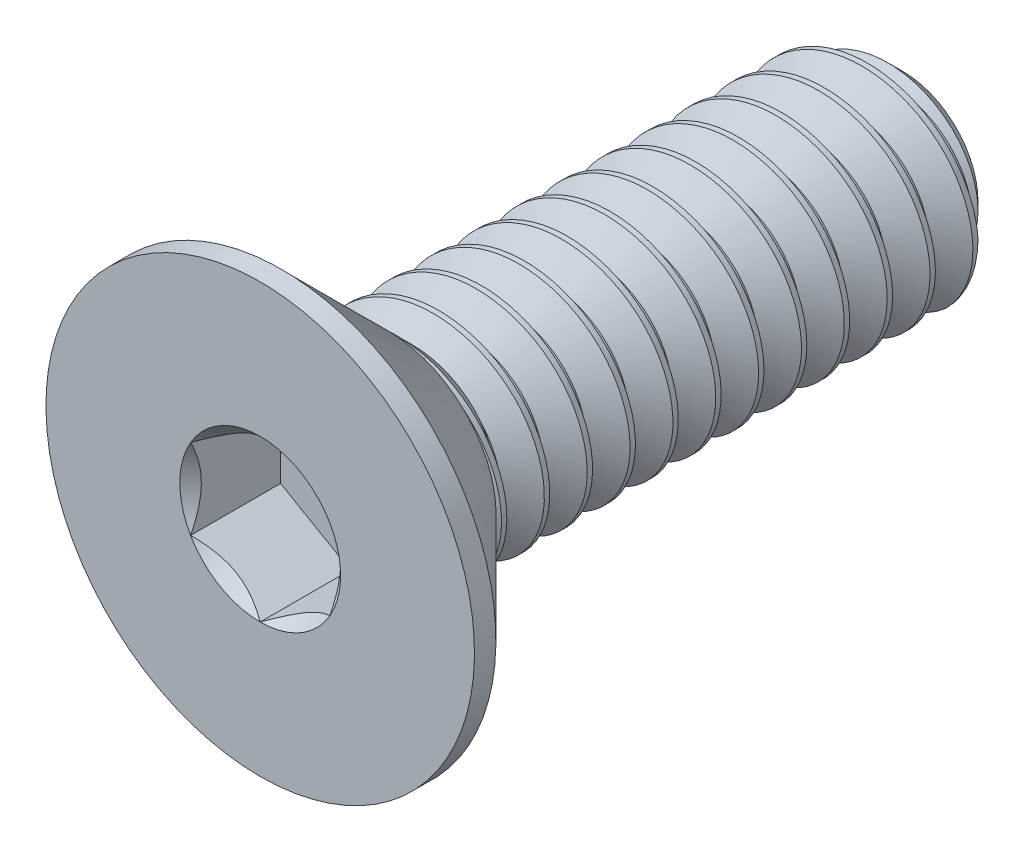
SolidWorks part; units mm, degrees
ref_plane "Front" through (0, 0, 0) normal (0, 0, 1) x (1, 0, 0)
ref_plane "Top" through (0, 0, 0) normal (0, 1, 0) x (1, 0, 0)
ref_plane "Right" through (0, 0, 0) normal (1, 0, 0) x (0, 0, -1)
sketch "Sketch1" plane through (0, 0, 0) normal (1, 0, 0) x (0, 0, -1)
  line L0 (0, 2) -> (0.2, 2) construction
  line L1 (0.2, 2) -> (1.2, 1) construction
  line L2 (0, 1) -> (6, 1)
  line L3 (6, 1) -> (6, 0)
  line L4 (6, 0) -> (0, 0)
  line L5 (0, 0) -> (0, 2) construction
  line L6 (0, 2) -> (0, -2) construction
  line L7 (6, 1) -> (6, -1) construction
  line L8 (0, -2) -> (0.2, -2) construction
  line L9 (0.2, -2) -> (1.2, -1) construction
  line L11 (0, 1) -> (0, 0)
  line L12 (1.2, 1) -> (1.2, 0) construction
  dimension "Head Ht" = 1.2
  dimension "Head Dia" = 4
  dimension "Dia" = 2
  dimension "Lg" = 6
  dimension "Head Angle" = 90
revolve "Revolve1" add sketch "Sketch1" angle 360 about L4
sketch "Sketch3" plane through (0, 0, -6) normal (0, 0, -1) x (-1, 0, 0)
  circle A0 centre (0, 0) radius 1
curve "Helix/Spiral1" pitch 0.4 height 6 radius 1 centre (0, 0, -6) axis (0, 0, 1) start towards (0, 1, 0)
sketch "Sketch2" plane through (0, 0, 0) normal (1, 0, 0) x (0, 0, -1)
  line L0 (6, 1) -> (6.35, 1)
  line L1 (6.35, 1) -> (6.2, 0.7402)
  line L2 (6.2, 0.7402) -> (6.15, 0.7402)
  line L3 (6.15, 0.7402) -> (6, 1)
  line L4 (6.075, 0.8701) -> (6.275, 0.8701) construction
  dimension "D1" = 60
  dimension "D2" = 0.05
  dimension "D3" = 0.2
chamfer "Chamfer1" distance 0.3 angle 45 1 edges at (0, 1, -6)
sweep "Cut-Sweep1" cut profiles "Sketch2" path "Helix/Spiral1"
sketch "Sketch7" plane through (0, 0, 0) normal (1, 0, 0) x (0, 0, -1)
  line L0 (0, 2) -> (0.2, 2) construction
  line L1 (0.2, 2) -> (1.2, 1) construction
  line L2 (0, 2) -> (0.2, 2)
  line L3 (0.2, 2) -> (1.2, 1)
  line L4 (1.2, 1) -> (1.2, 0) construction
  line L5 (1.2, 1) -> (1.2, 0)
  line L7 (0, 0) -> (0, 2) construction
  line L8 (0, 0) -> (0, 2)
  line L9 (0, 0) -> (1.2, 0)
  line L10 (2.2, 0) -> (-2.2, 0) construction
revolve "Revolve2" add sketch "Sketch7" angle 360 about L9
ref_plane "Plane1" through (0, 0, -1.2) normal (0, 0, 1) x (1, 0, 0)
sketch "Sketch8" plane through (0, 0, -1.2) normal (0, 0, 1) x (1, 0, 0)
  circle A0 centre (0, 0) radius 1
extrude "Boss-Extrude1" add sketch "Sketch8" against normal through all draft 45
sketch "Sketch5" plane through (0, 0, 0) normal (0, 0, 1) x (1, 0, 0)
  line L1 (0.65, -0.3753) -> (0.65, 0.3753)
  line L2 (0.65, 0.3753) -> (0, 0.7506)
  line L3 (0, 0.7506) -> (-0.65, 0.3753)
  line L4 (-0.65, 0.3753) -> (-0.65, -0.3753)
  line L5 (-0.65, -0.3753) -> (0, -0.7506)
  line L6 (0, -0.7506) -> (0.65, -0.3753)
  circle A0 centre (0, 0) radius 0.65 construction
  dimension "Hex" = 1.3
extrude "Cut-Extrude2" cut sketch "Sketch5" against normal blind 0.84
sketch "Sketch6" plane through (0, 0, 0) normal (0, 0, 1) x (1, 0, 0)
  circle A0 centre (0, 0) radius 0.7506
extrude "Cut-Extrude3" cut sketch "Sketch6" against normal blind 0.84 draft 45
sketch "Sketch9" [suppressed] plane through (0, 0, -5.5) normal (0, 0, 1) x (1, 0, 0)
  circle A1 centre (0, 0) radius 5
  circle A2 centre (0, 0) radius 5
  point P0 (0, 5)
  dimension "D1" = 0
extrude "Boss-Extrude2" [suppressed] add sketch "Sketch9" against normal offset from surface (18.5 mm away) 26 up to face at (0, 0.7, -6)
fillet "Fillet1" [suppressed] radius 0.2
sketch "Sketch10" plane through (0, 0, 0) normal (1, 0, 0) x (0, 0, -1)
  line L0 (6, 1) -> (6, -1) construction
  point P0 (5.4, -1)
  dimension "D1" = 0.6
equation "\"D3@Helix/Spiral1\" = \"Lg@Sketch1\""
equation "\"D2@Sketch2\" = \"D4@Helix/Spiral1\" * .125"
equation "\"D3@Sketch2\" = \"D4@Helix/Spiral1\" * .5"
equation "\"D1@Chamfer1\" = \"D4@Helix/Spiral1\" * .75"
equation "\"D1@Cut-Extrude2\" = \"Head Ht@Sketch1\" * .7"
equation "\"D1@Sketch10\" = \"D4@Helix/Spiral1\" * 1.5"
equation "\"D1@Cut-Extrude3\" = \"D1@Cut-Extrude2\""
equation "\"D1@Fillet1\" = \"Dia@Sketch1\" * .1"
